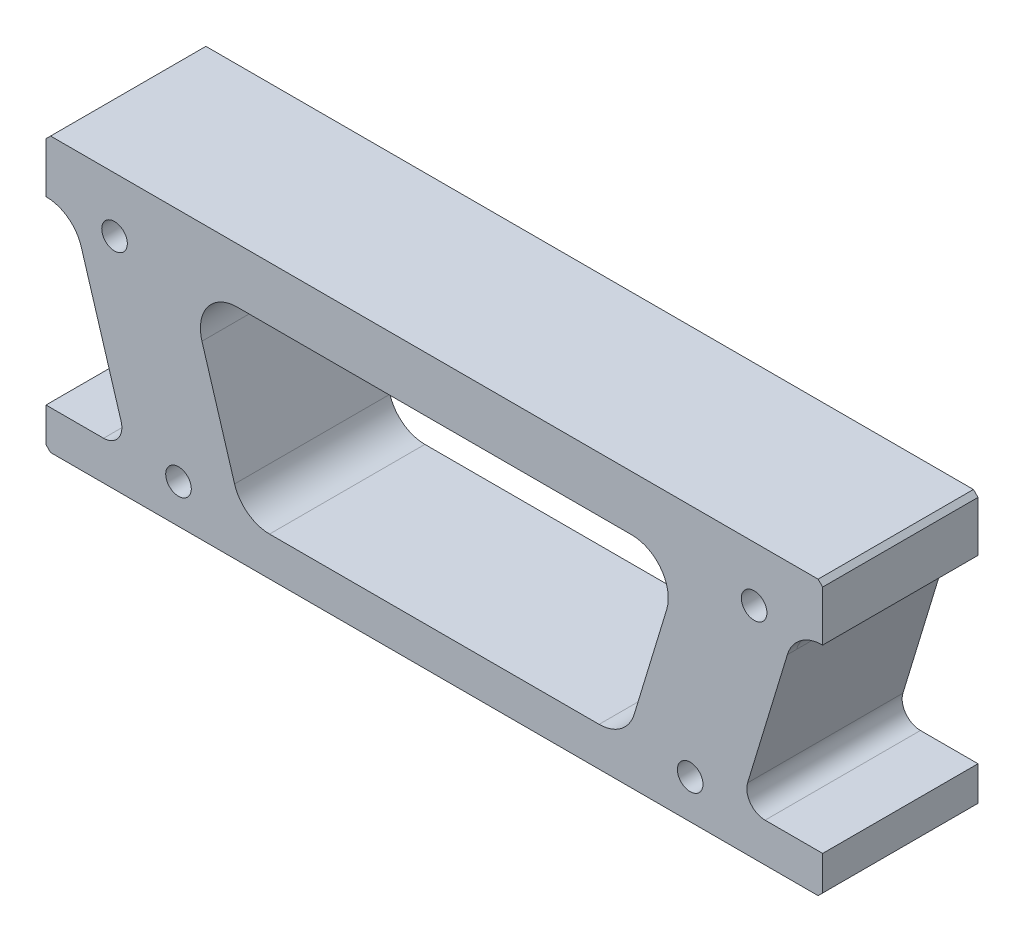
SolidWorks part; units mm, degrees
ref_plane "前视基准面" through (0, 0, 0) normal (0, 0, 1) x (1, 0, 0)
ref_plane "上视基准面" through (0, 0, 0) normal (0, 1, 0) x (1, 0, 0)
ref_plane "右视基准面" through (0, 0, 0) normal (1, 0, 0) x (0, 0, -1)
sketch "草图1" plane through (0, 0, 0) normal (0, 1, 0) x (1, 0, 0)
  line L1 (-42.5, 7.5) -> (42.5, 7.5)
  line L2 (-42.5, 7.5) -> (-42.5, -7.5)
  line L3 (-42.5, -7.5) -> (42.5, -7.5)
  line L4 (42.5, 7.5) -> (42.5, -7.5)
  line L5 (-42.5, 7.5) -> (42.5, -7.5) construction
  line L6 (-42.5, -7.5) -> (42.5, 7.5) construction
  dimension "D1" = 85
  dimension "D2" = 15
extrude "凸台-拉伸1" add sketch "草图1" along normal blind 30
sketch "草图2" plane through (0, 0, 7.5) normal (0, 0, 1) x (1, 0, 0)
  line L0 (0, 30) -> (0, 24) construction
  line L1 (0, 24) -> (-35, 24) construction
  line L2 (0, 24) -> (35, 24) construction
  line L3 (0, 24) -> (0, 4) construction
  line L4 (0, 4) -> (28, 4.2557) construction
  line L5 (0, 4) -> (-28, 4.2557) construction
  line L6 (0, 30) -> (0, 37.6117) construction
  line L7 (-42.5, 30) -> (42.5, 30) construction
  circle A0 centre (-35, 24) radius 1.4
  circle A1 centre (35, 24) radius 1.4
  circle A2 centre (28, 4.2557) radius 1.4
  circle A3 centre (-28, 4.2557) radius 1.4
extrude "切除-拉伸1" cut sketch "草图2" against normal blind 40
sketch "草图3" plane through (0, 0, 7.5) normal (0, 0, 1) x (1, 0, 0)
  line L0 (-27, 24) -> (27, 24)
  line L1 (-27, 24) -> (-21, 4.2557)
  line L2 (-21, 4.2557) -> (21, 4.2557)
  line L3 (0, 0) -> (0, 30) construction
  line L4 (-42.5, 30) -> (42.5, 30) construction
  line L5 (27, 24) -> (21, 4.2557)
  point P12 (0, 4.2557)
  point P13 (0, 24)
extrude "切除-拉伸2" cut sketch "草图3" against normal blind 40
fillet "圆角1" radius 4 4 edges at (-27, 24, 0) (27, 24, 0) (21, 4.2557, 0) (-21, 4.2557, 0)
sketch "草图5" plane through (0, 30, 0) normal (0, 1, 0) x (1, 0, 0)
  line L0 (-20, -4.5) -> (20, -4.5) construction
  line L1 (0, 4.5) -> (0, -4.5) construction
  line L2 (-35, 4.5) -> (0, 4.5) construction
  line L3 (0, 4.5) -> (35, 4.5) construction
  line L4 (0, 7.5) -> (0, 4.5) construction
  circle A0 centre (-35, 4.5) radius 1.8
  circle A1 centre (35, 4.5) radius 1.8
  circle A2 centre (-20, -4.5) radius 1.8
  circle A3 centre (20, -4.5) radius 1.8
  point P0 (0, 0)
extrude "切除-拉伸3" cut sketch "草图5" against normal blind 5
ref_plane "基准面1" through (0, 15, 0) normal (0, 1, 0) x (1, 0, 0)
chamfer "倒角1" distance 0.5 angle 45 4 edges at (-42.5, 0, 0) (42.5, 0, 0) (42.5, 30, 0) (-42.5, 30, 0)
sketch "草图6" plane through (0, 0, 7.5) normal (0, 0, 1) x (1, 0, 0)
  line L0 (-42.5, 24) -> (-39.5, 24)
  line L1 (-42.5, 29.5) -> (-42.5, 0.5) construction
  line L2 (-39.5, 24) -> (-33.5, 4.2557)
  line L3 (-33.5, 4.2557) -> (-42.5, 4.2557)
  line L4 (-25.431, 18.837) -> (-21.8621, 7.0927) construction
  line L5 (-25.431, 18.837) -> (-21.8621, 7.0927) construction
  line L6 (0, 30) -> (0, 0) construction
  line L7 (-42, 30) -> (42, 30) construction
  line L8 (-42.5, 24) -> (-42.5, 4.2557)
  line L9 (42.5, 24) -> (42.5, 4.2557)
  line L10 (33.5, 4.2557) -> (42.5, 4.2557)
  line L11 (39.5, 24) -> (33.5, 4.2557)
  line L12 (42.5, 24) -> (39.5, 24)
extrude "切除-拉伸4" cut sketch "草图6" against normal blind 24
fillet "圆角3" radius 4 2 edges at (39.5, 24, 0) (-39.5, 24, 0)
sketch "草图9" plane through (0, 0, 0) normal (0, -1, 0) x (1, 0, 0)
  circle A0 centre (20, 4.5) radius 1.8 construction
  circle A1 centre (-20, 4.5) radius 1.8 construction
  circle A2 centre (-35, -4.5) radius 1.8 construction
  circle A3 centre (35, -4.5) radius 1.8 construction
  circle A4 centre (20, 4.5) radius 1.8
  circle A5 centre (-20, 4.5) radius 1.8
  circle A6 centre (-35, -4.5) radius 1.8
  circle A7 centre (35, -4.5) radius 1.8
extrude "切除-拉伸5" cut sketch "草图9" against normal blind 5
fillet "圆角4" radius 2 2 edges at (-33.5, 4.2557, 1.9975) (33.5, 4.2557, 1.9975)
sketch "草图10" plane through (0, 0, -7.5) normal (0, 0, -1) x (-1, 0, 0)
  line L0 (42, 30) -> (-42, 30)
  line L1 (-42, 30) -> (-42.5, 29.5)
  line L2 (-42.5, 29.5) -> (-42.5, 24)
  line L3 (-38.6379, 21.163) -> (-34.2845, 6.8372)
  line L4 (-36.1981, 4.2557) -> (-42.5, 4.2557)
  line L5 (-42.5, 4.2557) -> (-42.5, 0.5)
  line L6 (-42.5, 0.5) -> (-42, 0)
  line L7 (-42, 0) -> (42, 0)
  line L8 (42, 0) -> (42.5, 0.5)
  line L9 (42.5, 0.5) -> (42.5, 4.2557)
  line L10 (42.5, 4.2557) -> (36.1981, 4.2557)
  line L11 (34.2845, 6.8372) -> (38.6379, 21.163)
  line L12 (42.5, 24) -> (42.5, 29.5)
  line L13 (42.5, 29.5) -> (42, 30)
  line L14 (21.6038, 24) -> (-21.6038, 24)
  line L15 (18.0349, 4.2557) -> (-18.0349, 4.2557)
  line L16 (25.431, 18.837) -> (21.8621, 7.0927)
  line L17 (-25.431, 18.837) -> (-21.8621, 7.0927)
  line L18 (-34.2845, 6.8372) -> (-40.1361, 26.0931)
  line L19 (-42.5, 24) -> (-39.5, 24)
  line L20 (34.2845, 6.8372) -> (39.7719, 24.8948)
  line L21 (42.5, 24) -> (39.5, 24)
  arc A1 (34.2845, 6.8372) -> (36.1981, 4.2557) centre (36.1981, 6.2557) ccw
  arc A3 (-34.2845, 6.8372) -> (-36.1981, 4.2557) centre (-36.1981, 6.2557) cw
  arc A4 (21.6038, 24) -> (25.431, 18.837) centre (21.6038, 20) cw
  arc A5 (21.8621, 7.0927) -> (18.0349, 4.2557) centre (18.0349, 8.2557) cw
  arc A6 (-21.6038, 24) -> (-25.431, 18.837) centre (-21.6038, 20) ccw
  arc A7 (-21.8621, 7.0927) -> (-18.0349, 4.2557) centre (-18.0349, 8.2557) ccw
  circle A8 centre (35, 24) radius 1.4
  circle A9 centre (28, 4.2557) radius 1.4
  circle A10 centre (-28, 4.2557) radius 1.4
  circle A11 centre (-35, 24) radius 1.4
  line M19 (-42.5, 29.5) -> (-42.5, 24)
  line M20 (-42.5, 24) -> (-42.4651, 24)
  line M22 (-38.6379, 21.163) -> (-34.2845, 6.8372)
  arc M23 (-34.2845, 6.8372) -> (-36.1981, 4.2557) centre (-36.1981, 6.2557) cw
  line M24 (-36.1981, 4.2557) -> (-42.5, 4.2557)
  line M25 (-42.5, 4.2557) -> (-42.5, 0.5)
  line M26 (-42.5, 0.5) -> (-42, 0)
  line M27 (-42, 0) -> (42, 0)
  line M28 (42, 0) -> (42.5, 0.5)
  line M29 (42.5, 0.5) -> (42.5, 4.2557)
  line M30 (42.5, 4.2557) -> (36.1981, 4.2557)
  arc M31 (36.1981, 4.2557) -> (34.2845, 6.8372) centre (36.1981, 6.2557) cw
  line M32 (34.2845, 6.8372) -> (38.6379, 21.163)
  line M34 (42.4651, 24) -> (42.5, 24)
  line M35 (42.5, 24) -> (42.5, 29.5)
  line M36 (42.5, 29.5) -> (42, 30)
  line M37 (42, 30) -> (-42, 30)
  line M38 (-42, 30) -> (-42.5, 29.5)
  line M39 (-21.8621, 7.0927) -> (-25.431, 18.837)
  arc M40 (-25.431, 18.837) -> (-21.6038, 24) centre (-21.6038, 20) cw
  line M41 (-21.6038, 24) -> (21.6038, 24)
  arc M42 (21.6038, 24) -> (25.431, 18.837) centre (21.6038, 20) cw
  line M43 (25.431, 18.837) -> (21.8621, 7.0927)
  arc M44 (21.8621, 7.0927) -> (18.0349, 4.2557) centre (18.0349, 8.2557) cw
  line M45 (18.0349, 4.2557) -> (-18.0349, 4.2557)
  arc M46 (-18.0349, 4.2557) -> (-21.8621, 7.0927) centre (-18.0349, 8.2557) cw
  circle M47 centre (28, 4.2557) radius 1.4
  circle M48 centre (-28, 4.2557) radius 1.4
  circle M49 centre (-35, 24) radius 1.4
  circle M50 centre (35, 24) radius 1.4
  dimension "D1" = 2.8
extrude "凸台-拉伸3" add sketch "草图10" along normal blind 1 and the other way blind 16 contours L21 L19 L18 L20 M34 M35 M36 M37 M38 M19 M20 M22 M23 M24 M25 M26 M27 M28 M29 M30 M31 M32 M46 M39 M40 M41 M42 M43 M44 M45 M47 M49 M50 M48 region at (-41.6126, 29.1126, -7.5)
fillet "圆角5" radius 4 4 edges at (39.5, 24, -8) (39.5, 24, 8) (-39.5, 24, -8) (-39.5, 24, 8)
